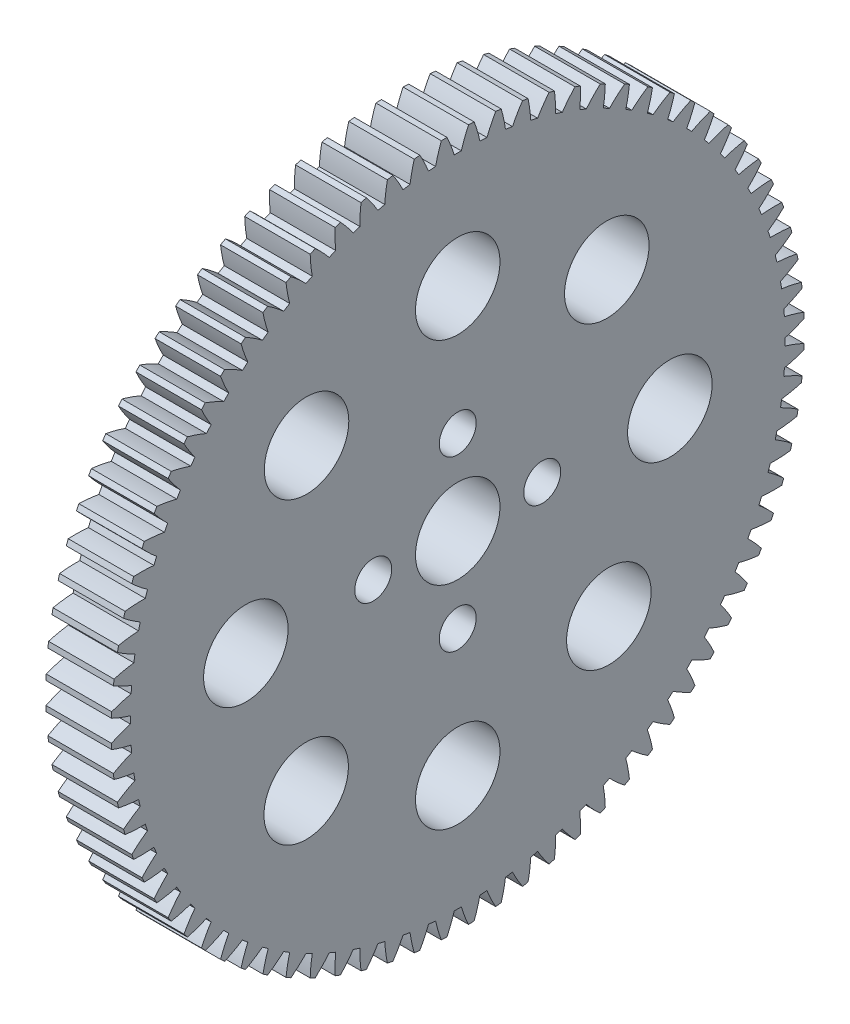
SolidWorks part; units mm, degrees
material "6061 Alloy"
ref_plane "Plane1" through (0, 0, 0) normal (0, 0, 1) x (1, 0, 0)
ref_plane "Plane2" through (0, 0, 0) normal (0, 1, 0) x (1, 0, 0)
ref_plane "Plane3" through (0, 0, 0) normal (1, 0, 0) x (0, 0, -1)
sketch "HoldingSke" plane through (0, 0, 0) normal (0, 1, 0) x (1, 0, 0)
  line L0 (0, 0) -> (0.2171, -1.231)
  line L1 (-15, 0) -> (100, 0) construction
  line L2 (0, 0) -> (-2.1039, 2.3779)
  line L3 (0, 0) -> (-11.863, 4.5341)
  line L4 (0, 0) -> (1.4996, 8.5048)
  line L5 (0, 0) -> (-46.8476, -17.4728)
  line L6 (0, 0) -> (-5.1396, -3.4677)
  line L7 (-2.1039, 2.3779) -> (8.6586, 51.2059)
  line L8 (-76.2, 54.61) -> (-74.8, 54.61)
  line L9 (-71.009, 38.7566) -> (-53.1078, 45.2721)
  line L10 (-76.2, 71.12) -> (104.1128, 71.12)
  line L11 (0, 0) -> (-6.2, 0)
  line L12 (-76.2, 101.6) -> (-76.17, 101.6)
  line L13 (24.9733, 27.94) -> (52.9518, 28.4284)
  line L14 (24.9733, 27.94) -> (24.9743, 27.94)
  line L15 (24.9733, 27.94) -> (100.4006, 29.5858)
  line L16 (-63.627, -0.8) -> (-12.827, -0.8)
  circle A0 centre (0, 0) radius 4
  circle A1 centre (0, 0) radius 30.999
  circle A2 centre (0, 0) radius 37.5
  circle A3 centre (0, 0) radius 4
  dimension "MHD" = 61.998
  dimension "Hub_dia" = 75
  dimension "Bore" = 8
  dimension "MBD" = 8
  dimension "Num_teeth" = 80
  dimension "Pitch_radius" = 180.3128
  dimension "Pitch" = 1.25
  dimension "Width" = 6.2
  dimension "Overall_len" = 50
  dimension "Show_teeth" = 80
  dimension "Thickness" = 6.2
  dimension "OAL" = 50.0001
  dimension "T_dim" = 1.4
  dimension "Ap" = 20
  dimension "H" = 19.05
  dimension "Backlash" = 0.03
  dimension "Addendum_fac" = 1
  dimension "Dedendum_fac" = 1.25
  dimension "Clearance_fac" = 0.25
  dimension "Dedendum_add" = 0.001
  dimension "Module" = 0.8
sketch "BasProSke" plane through (0, 0, 0) normal (0, 1, 0) x (1, 0, 0)
  line L0 (-10, 0) -> (60, 0) construction
  line L1 (0, 0) -> (0, 32.8)
  line L2 (0, 0) -> (6.2, 0)
  line L3 (6.2, 0) -> (6.2, 32.8)
  line L4 (6.2, 32.8) -> (0, 32.8)
  dimension "Diameter" = 65.6
  dimension "Thickness" = 6.2
revolve "Base-Revolve" add sketch "BasProSke" angle 360 about L0
sketch "TooCutSke" plane through (0, 0, 0) normal (1, 0, 0) x (0, 0, -1)
  line L1 (0, 0) -> (0, 107) construction
  line L2 (0, 0) -> (-0.6808, 31.9928) construction
  line L3 (0, 0) -> (-2.5122, 63.9403) construction
  line L4 (-0.6808, 31.9928) -> (-1.2561, 31.9702) construction
  arc A0 (0.3357, 30.9972) -> (-0.3357, 30.9972) centre (0, 0) ccw
  arc A1 (1.0352, 32.8091) -> (-1.0352, 32.8091) centre (0, 0) ccw
  circle A2 centre (0, 0) radius 32 construction
  circle A3 centre (0, 0) radius 30.0702 construction
  arc A4 (-0.3357, 30.9972) -> (-1.0352, 32.8091) centre (-12.5921, 27.3066) ccw
  arc A5 (1.0352, 32.8091) -> (0.3357, 30.9972) centre (12.5921, 27.3066) ccw
  dimension "Root_dia" = 61.998
  dimension "Overcut_dia" = 65.6508
  dimension "Pitch_dia" = 64
  dimension "Base_dia" = 60.1403
  dimension "Flank_rad" = 12.8
  dimension "Half_ang" = 2.25
  dimension "Half_CT" = 0.5758
extrude "ToothCut" cut sketch "TooCutSke" along normal through all
fillet "Breaks" [suppressed] radius 0.016 tangent propagation no
fillet "RootFillets" [suppressed] radius 0.201
pattern_circular "TeethCuts" count 80 every 4.5 about axis through (-10, 0, 0) along (1, 0, 0) of "ToothCut", "RootFillets", "Breaks"
sketch "HubNeaOneSke" plane through (0, 0, 0) normal (-1, 0, 0) x (0, 0, 1)
  circle A0 centre (0, 0) radius 30.999
  dimension "Diameter" = 61.998
extrude "HubNearOne" [suppressed] add sketch "HubNeaOneSke" along normal blind 43.8001
sketch "HubNeaBotSke" plane through (0, 0, 0) normal (-1, 0, 0) x (0, 0, 1)
  circle A0 centre (0, 0) radius 30.999
  dimension "Diameter" = 61.998
extrude "HubNearBoth" [suppressed] add sketch "HubNeaBotSke" along normal blind 21.9
ref_plane "FarPln" through (6.2, 0, 0) normal (1, 0, 0) x (0, 0, -1)
sketch "HubFarSke" plane through (6.2, 0, 0) normal (1, 0, 0) x (0, 0, -1)
  circle A0 centre (0, 0) radius 30.999
  dimension "Diameter" = 61.998
extrude "HubFar" [suppressed] add sketch "HubFarSke" along normal blind 21.9
sketch "BorSke" plane through (0, 0, 0) normal (1, 0, 0) x (0, 0, -1)
  circle A0 centre (0, 0) radius 4
  dimension "Diameter" = 8
extrude "Bore" cut sketch "BorSke" along normal mid plane 100.0001
sketch "KeySke" plane through (0, 0, 0) normal (1, 0, 0) x (0, 0, -1)
  line L0 (-1.5, 0) -> (-1.5, 5.4)
  line L1 (-1.5, 5.4) -> (1.5, 5.4)
  line L2 (1.5, 5.4) -> (1.5, 0)
  line L3 (0, 0) -> (0, 34) construction
  line L4 (-1.5, 0) -> (1.5, 0)
  dimension "Offset" = 5.4
  dimension "Width" = 3
extrude "Keyway" [suppressed] cut sketch "KeySke" along normal mid plane 100.0001
pattern_circular "Keyway2" [suppressed] count 2 every 90 about axis through (-10, 0, 0) along (1, 0, 0)
sketch "Sketch1" plane through (6.2, 0, 0) normal (1, 0, 0) x (0, 0, -1)
  line L0 (0, 0) -> (28.2252, 28.7327) construction
  line L1 (0, 0) -> (-25.3201, -24.9439) construction
  line L2 (0, 0) -> (24.7366, -24.4515) construction
  line L3 (0, 0) -> (-25.836, 25.5556) construction
  circle A0 centre (0, 20.084) radius 4
  circle A1 centre (0, -20.0633) radius 4
  circle A2 centre (20.084, 0) radius 4
  circle A3 centre (-20.0633, 0) radius 4
  circle A4 centre (14.1126, 14.3663) radius 4
  circle A5 centre (14.3069, -14.142) radius 4
  circle A6 centre (-14.3483, -14.1351) radius 4
  circle A7 centre (-14.315, 14.1597) radius 4
  circle A8 centre (0, 8) radius 1.75
  circle A9 centre (0, -8) radius 1.75
  circle A10 centre (8, 0) radius 1.75
  circle A11 centre (-8, 0) radius 1.75
  dimension "D1" = 8
  dimension "D2" = 8
  dimension "D3" = 8
  dimension "D4" = 8
  dimension "D5" = 8
  dimension "D6" = 8
  dimension "D7" = 8
  dimension "D8" = 8
  dimension "D17" = 3.5
  dimension "D18" = 3.5
  dimension "D19" = 3.5
  dimension "D20" = 3.5
  dimension "D9" = 12.7
  dimension "D10" = 12.7
  dimension "D11" = 12.7
  dimension "D12" = 12.7
  dimension "D13" = 12.7
  dimension "D14" = 12.7
  dimension "D15" = 12.7
  dimension "D16" = 12.7
  dimension "D21" = 8
  dimension "D22" = 8
  dimension "D23" = 8
  dimension "D24" = 8
extrude "Cut-Extrude1" cut sketch "Sketch1" against normal through all
equation "' \"Module@HoldingSke\" = 6.35"
equation "' \"Num_teeth@HoldingSke\" = 12"
equation "' \"Ap@HoldingSke\" =  20"
equation "' \"Width@HoldingSke\" = 0.5 * 25.4"
equation "' \"Hub_dia@HoldingSke\"= 1 * 25.4"
equation "' \"Overall_len@HoldingSke\" = 1.0 * 25.4"
equation "' \"Bore@HoldingSke\" = 0.75 * 25.4"
equation "' \"T_dim@HoldingSke\" = 0.1 * 25.4"
equation "' \"Width@KeySke\" = 0.25 * 25.4"
equation "' \"Show_teeth@HoldingSke\" = 13"
equation "' \"Backlash@HoldingSke\" = 0.009 * 25.4"
equation "' \"Addendum_fac@HoldingSke\" = 1.0"
equation "' \"Dedendum_fac@HoldingSke\" = 1.25"
equation "' \"Dedendum_add@HoldingSke\" = 0.00005 * 25.4"
equation "' \"Clearance_fac@HoldingSke\" = 0.25"
equation "\"Pitch@HoldingSke\" = 1 / \"Module@HoldingSke\""
equation "\"Overcut_dia@TooCutSke\" = (\"Num_teeth@HoldingSke\" + 2 * \"Addendum_fac@HoldingSke\") / \"Pitch@HoldingSke\" + 0.002 * 25.4"
equation "\"Pitch_dia@TooCutSke\" = \"Num_teeth@HoldingSke\" / \"Pitch@HoldingSke\""
equation "\"Base_dia@TooCutSke\" = \"Num_teeth@HoldingSke\" / \"Pitch@HoldingSke\" * cos((\"Ap@HoldingSke\"  * 3.14159265 / 180))"
equation "\"Root_dia@TooCutSke\" = (\"Num_teeth@HoldingSke\" + 2) / \"Pitch@HoldingSke\" - 2 * (\"Addendum_fac@HoldingSke\" + \"Dedendum_fac@HoldingSke\") / \"Pitch@HoldingSke\" - \"Dedendum_add@HoldingSke\" * 2"
equation "\"Half_ang@TooCutSke\" = 180 / \"Num_teeth@HoldingSke\""
equation "\"Half_CT@TooCutSke\" = \"Num_teeth@HoldingSke\" / \"Pitch@HoldingSke\" * sin((3.14159265 / 2 / \"Num_teeth@HoldingSke\")) / 2 - 7 * \"Backlash@HoldingSke\" / 4"
equation "\"Flank_rad@TooCutSke\" = \"Num_teeth@HoldingSke\" / \"Pitch@HoldingSke\" / 5"
equation "\"Radius@RootFillets\" = \"Clearance_fac@HoldingSke\" / \"Pitch@HoldingSke\" + \"Dedendum_add@HoldingSke\""
equation "\"Break_rad@Breaks\" = 0.02 / \"Pitch@HoldingSke\""
equation "\"Thickness@HoldingSke\" = \"Width@HoldingSke\""
equation "\"OAL@HoldingSke\" = \"Thickness@HoldingSke\""
equation "\"MHD@HoldingSke\" = (\"Num_teeth@HoldingSke\" + 2) / \"Pitch@HoldingSke\" - 2 * (\"Addendum_fac@HoldingSke\" + \"Dedendum_fac@HoldingSke\")  / \"Pitch@HoldingSke\" - \"Dedendum_add@HoldingSke\" * 2"
equation "\"MBD@HoldingSke\" = (\"Num_teeth@HoldingSke\" + 2) / \"Pitch@HoldingSke\" - 2 * (\"Addendum_fac@HoldingSke\" + \"Dedendum_fac@HoldingSke\")  / \"Pitch@HoldingSke\" - \"Dedendum_add@HoldingSke\" * 2 - 0.002 * 25.4"
equation "\"MHD@HoldingSke\" = ((sgn( \"MHD@HoldingSke\" - \"Hub_dia@HoldingSke\" )-1)*( \"MHD@HoldingSke\" - \"Hub_dia@HoldingSke\" ))/-2+ \"Hub_dia@HoldingSke\""
equation "\"MBD@HoldingSke\" = ((sgn( \"MBD@HoldingSke\" - \"Bore@HoldingSke\" )-1)*( \"MBD@HoldingSke\" - \"Bore@HoldingSke\" ))/-2+ \"Bore@HoldingSke\""
equation "\"OAL@HoldingSke\" = ((sgn( \"OAL@HoldingSke\" - \"Overall_len@HoldingSke\" )+1)*( \"OAL@HoldingSke\" - \"Overall_len@HoldingSke\" ))/2 + \"Overall_len@HoldingSke\" + 0.000002 * 25.4"
equation "\"Num_teeth@TeethCuts\" = int( \"Show_teeth@HoldingSke\" ) + 1"
equation "\"Num_teeth@TeethCuts\" = ((sgn( \"Num_teeth@TeethCuts\" - \"Num_teeth@HoldingSke\" )-1)*( \"Num_teeth@TeethCuts\" - \"Num_teeth@HoldingSke\" ))/-2+ \"Num_teeth@HoldingSke\""
equation "\"Num_teeth@TeethCuts\" = ((sgn( \"Num_teeth@TeethCuts\" - 2.0)+1)*( \"Num_teeth@TeethCuts\" - 2.0))/2 +2.0"
equation "\"Angle@TeethCuts\" = 360.0 / \"Num_teeth@HoldingSke\""
equation "\"Diameter@BasProSke\" = (\"Num_teeth@HoldingSke\" + 2 * \"Addendum_fac@HoldingSke\") / \"Pitch@HoldingSke\""
equation "\"Thickness@BasProSke\"  = \"Thickness@HoldingSke\""
equation "' \"Fillet_rad@BasProSke\" =  \"Thickness@HoldingSke\" * 0.05"
equation "\"MHD@HoldingSke\" = ((sgn( \"MHD@HoldingSke\" - \"Root_dia@TooCutSke\" )-1)*( \"MHD@HoldingSke\" - \"Root_dia@TooCutSke\" ))/-2+ \"Root_dia@TooCutSke\""
equation "\"Diameter@HubNeaOneSke\" = \"MHD@HoldingSke\""
equation "\"Length@HubNearOne\" = \"OAL@HoldingSke\" - \"Thickness@BasProSke\""
equation "\"Diameter@HubNeaBotSke\" = \"MHD@HoldingSke\""
equation "\"Length@HubNearBoth\" = ( \"OAL@HoldingSke\" - \"Thickness@BasProSke\" ) / 2.0"
equation "\"Thickness@FarPln\" = \"Thickness@BasProSke\""
equation "\"Diameter@HubFarSke\" = \"MHD@HoldingSke\""
equation "\"Length@HubFar\" = ( \"OAL@HoldingSke\" - \"Thickness@BasProSke\" ) / 2.0"
equation "\"Diameter@BorSke\" = \"MBD@HoldingSke\""
equation "\"D1@Bore\" = \"OAL@HoldingSke\" * 2.0"
equation "\"D1@Keyway\" = \"OAL@HoldingSke\" * 2.0"
equation "\"Offset@KeySke\" = \"T_dim@HoldingSke\" + \"MBD@HoldingSke\" / 2.0"
